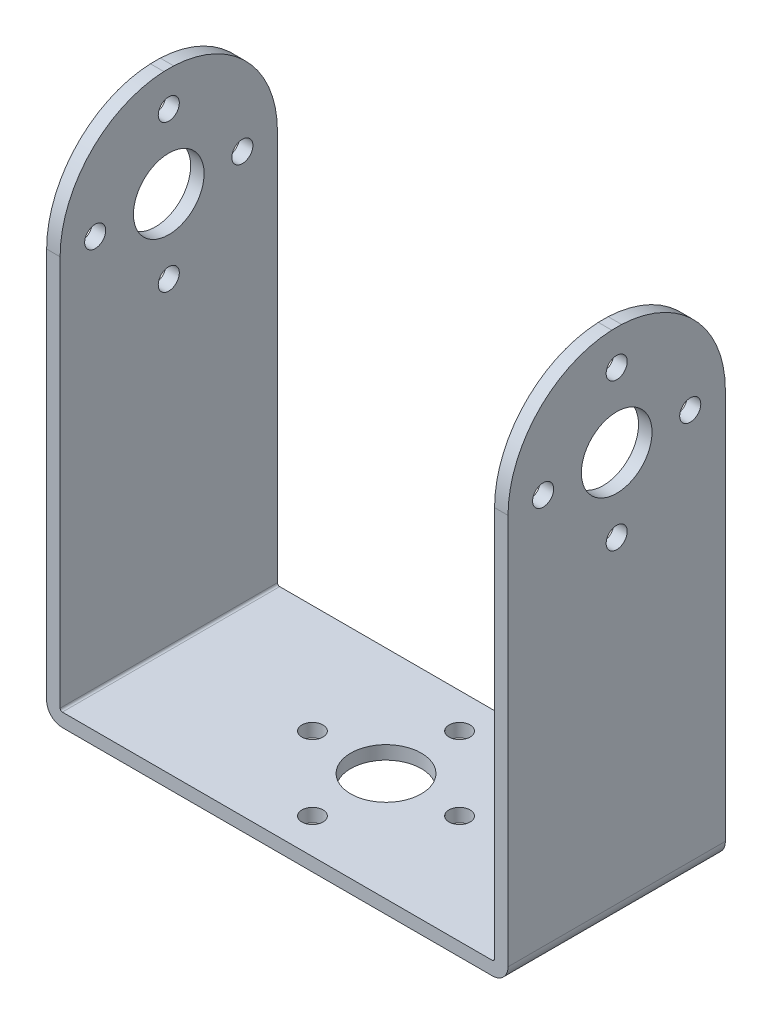
SolidWorks part; units mm, degrees
note: The reader was unsure of these and kept them because the rebuilt part matched: shared geometry of "Sketch1<3>".
ref_plane "Front" through (0, 0, 0) normal (0, 0, 1) x (1, 0, 0)
ref_plane "Top" through (0, 0, 0) normal (0, 1, 0) x (1, 0, 0)
ref_plane "Right" through (0, 0, 0) normal (1, 0, 0) x (0, 0, -1)
sketch "Sketch1" plane through (0, 0, 0) normal (0, 1, 0) x (1, 0, 0)
  line L0 (26.1239, 12.3063) -> (26.1239, -12.3063)
  line L9 (26.1239, -12.3063) -> (-26.1239, -12.3063)
  line L10 (-26.1239, 12.3063) -> (26.1239, 12.3063)
  line L11 (-26.1239, -12.3063) -> (-26.1051, -12.1887)
  line L12 (26.1239, -12.3063) -> (26.1051, -12.1887)
  line L13 (-24.5999, -12.3063) -> (-24.5999, 12.3063)
  line L14 (-26.1239, 12.3063) -> (-26.1239, -12.3063)
  line L15 (24.5999, -12.3063) -> (24.5999, 12.3063)
  circle A5 centre (0, 8.3312) radius 1.1938
  circle A6 centre (-8.3312, 0) radius 1.1938
  circle A7 centre (0, 0) radius 4.0005
  circle A8 centre (8.3312, 0) radius 1.1938
  circle A9 centre (0, -8.3312) radius 1.1938
  point P43 (0, 12.3063)
extrude "Extrude1" add sketch "Sketch1" along normal blind 1.524
extrude "Extrude2" add sketch "Sketch1<3>" along normal blind 58.3438
sketch "Sketch1<3>" plane through (0, 0, 0) normal (0, 1, 0) x (1, 0, 0) same geometry as "Sketch1"
sketch "Sketch4" plane through (0, 0, 0) normal (1, 0, 0) x (0, 0, -1)
  line L0 (-12.3063, 58.3438) -> (-12.3063, 46.0502)
  line L1 (-12.3063, 58.3438) -> (12.3063, 58.3438)
  line L2 (12.3063, 58.3438) -> (12.3063, 46.0502)
  line L3 (0, 0) -> (0, 46.0502)
  arc A0 (12.3063, 46.0502) -> (-12.3063, 46.0502) centre (0, 46.0502) ccw
  circle A1 centre (0, 46.0629) radius 4.0005
  circle A3 centre (0, 54.3941) radius 1.1938
  circle A4 centre (8.3312, 46.0629) radius 1.1938
  circle A5 centre (-8.3312, 46.0629) radius 1.1938
  circle A6 centre (0, 37.7317) radius 1.1938
extrude "Cut-Extrude1" cut sketch "Sketch4" against normal blind 40.8686 and the other way blind 40.8686 contours L0 A0 L1 | L1 A0 L2 | A1 | A4 | A3 | A5 | A6
fillet "Fillet1" radius 0.254 2 edges
fillet "Fillet2" radius 1.778 2 edges at (-26.1239, 0, 0) (26.1239, 0, 0)
